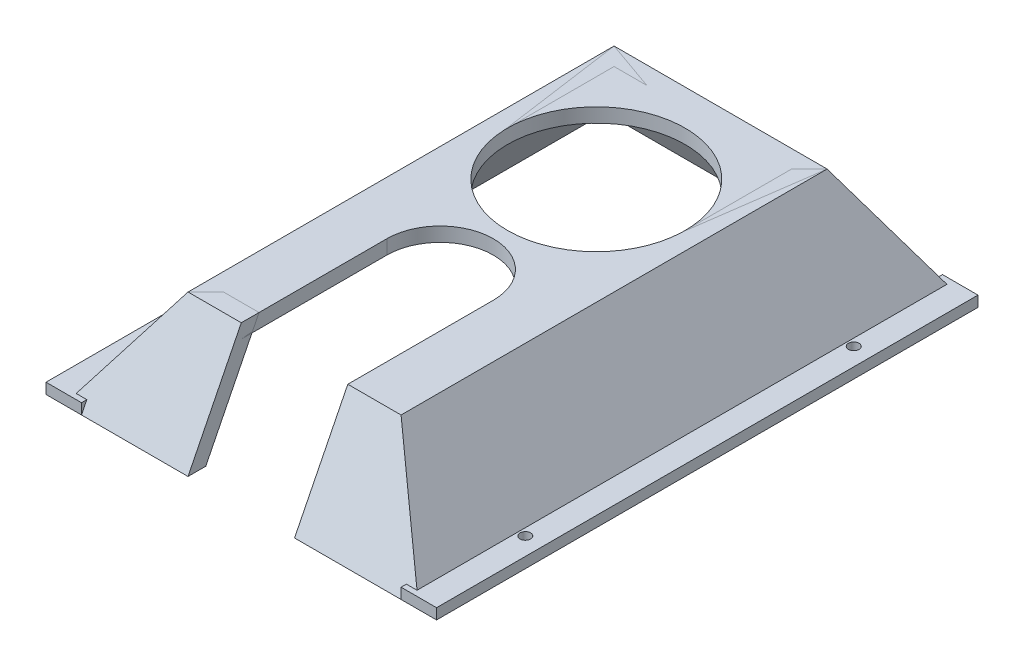
SolidWorks part; units mm, degrees
ref_plane "Front Plane" through (0, 0, 0) normal (0, 0, 1) x (1, 0, 0)
ref_plane "Top Plane" through (0, 0, 0) normal (0, 1, 0) x (1, 0, 0)
ref_plane "Right Plane" through (0, 0, 0) normal (1, 0, 0) x (0, 0, -1)
sketch "Sketch1" plane through (0, 0, 0) normal (0, 1, 0) x (1, 0, 0)
  line L20 (-50, 152.5) -> (50, 152.5)
  line L21 (-50, 152.5) -> (-50, 0)
  line L22 (-50, 0) -> (50, 0)
  line L23 (50, 152.5) -> (50, 0)
  point P4 (0, 0)
  dimension "D1" = 152.5
  dimension "D2" = 100
ref_plane "Plane1" through (0, 30, 0) normal (0, 1, 0) x (1, 0, 0)
sketch "Sketch3" plane through (0, 30, 0) normal (0, 1, 0) x (1, 0, 0)
  line L1 (-30, 135) -> (30, 135)
  line L2 (-30, 135) -> (-30, 15)
  line L3 (-30, 15) -> (30, 15)
  line L4 (30, 135) -> (30, 15)
  point P4 (0, 15)
  dimension "D1" = 120
  dimension "D2" = 60
  dimension "D3" = 15
loft "Loft8" add profiles "Sketch1", "Sketch3" connector at (50, 0, -152.5) connector at (30, 30, -135)
sketch "Sketch4" plane through (0, 30, 0) normal (0, 1, 0) x (1, 0, 0)
  line L0 (30, 135) -> (-30, 135) construction
  line L1 (-25, 130) -> (25, 130)
  line L2 (-25, 130) -> (-25, 20)
  line L3 (-25, 20) -> (25, 20)
  line L4 (25, 130) -> (25, 20)
  line L5 (-30, 15) -> (30, 15) construction
  line L6 (-30, 135) -> (-30, 15) construction
  point P8 (0, 20)
  dimension "D1" = 5
  dimension "D2" = 5
  dimension "D3" = 5
sketch "Sketch5" plane through (0, 0, 0) normal (0, 1, 0) x (1, 0, 0)
  line L0 (-50, 0) -> (50, 0) construction
  line L1 (-45, 147.5) -> (45, 147.5)
  line L2 (-45, 147.5) -> (-45, 5)
  line L3 (-45, 5) -> (45, 5)
  line L4 (45, 147.5) -> (45, 5)
  line L5 (-50, 152.5) -> (50, 152.5) construction
  line L6 (50, 152.5) -> (50, 0) construction
  point P10 (0, 5)
  dimension "D1" = 5
  dimension "D2" = 5
  dimension "D3" = 5
loft "Cut-Loft1" cut profiles "Sketch4", "Sketch5" connector at (25, 30, -130) connector at (45, 0, -147.5)
sketch "Sketch6" plane through (0, 0, 0) normal (0, 1, 0) x (1, 0, 0)
  line L14 (-45, 152.5) -> (-55, 152.5)
  line L15 (-50, 152.5) -> (50, 152.5) construction
  line L16 (-55, 152.5) -> (-55, 0)
  line L17 (-55, 0) -> (-45, 0)
  line L18 (-50, 0) -> (50, 0) construction
  line L19 (-45, 0) -> (-45, 152.5)
  line L20 (0, 150) -> (0, 0) construction
  line L21 (55, 0) -> (45, 0)
  line L22 (55, 152.5) -> (55, 0)
  line L23 (45, 152.5) -> (55, 152.5)
  line L24 (45, 0) -> (45, 152.5)
  line L25 (-50, 0) -> (-50, 30)
  line L26 (-50, 152.5) -> (-50, 122.5)
  point P10 (-50, 30)
  point P11 (-50, 122.5)
  point P26 (50, 30)
  point P27 (50, 122.5)
  dimension "D1" = 10
  dimension "D2" = 152.5
  dimension "D3" = 45
  dimension "D5" = 30
extrude "Boss-Extrude2" add sketch "Sketch6" along normal blind 3 contours L17 L19 L14 L16 | L24 L21 L22 L23 region at (-50, 0, -76.25) region at (50, 0, -76.25)
hole_wizard "Ø3.0mm Dowel Hole1" positions "Sketch9" profile "Sketch10" hole size "Ø3.0" standard "ANSI Metric" end condition through all
sketch "Sketch9" plane through (0, 3, 0) normal (0, 1, 0) x (1, 0, 0)
  point P0 (50, 30)
  point P3 (-50, 30)
  point P6 (-50, 122.5)
  point P9 (50, 122.5)
sketch "Sketch10" plane through (50, 3, -30) normal (1, 0, 0) x (0, 0, 1)
  line L0 (0, 0) -> (0, 3.0001)
  line L1 (0, 3.0001) -> (1.5, 3.0001)
  line L2 (1.5, 3.0001) -> (1.5, 0)
  line L5 (1.5, 0) -> (0, 0)
  line L11 (0, -6.35) -> (0, 107.95) construction
  dimension "Thru Hole Dia." = 3
  dimension "Thru Hole Depth" = 3.0001
sketch "Sketch12" plane through (0, 30, 0) normal (0, 1, 0) x (1, 0, 0)
  line L0 (-15, 56) -> (-15, 15)
  line L2 (0, 1) -> (0, 63.6102) construction
  line L7 (15, 56) -> (15, 15)
  line L12 (-30, 135) -> (30, 135)
  line L13 (-30, 135) -> (-30, 15)
  line L14 (-30, 15) -> (30, 15)
  line L15 (30, 135) -> (30, 15)
  arc A0 (-15, 56) -> (15, 56) centre (0, 56) cw
  circle A2 centre (0, 100) radius 25
  point P16 (0, 71)
  dimension "D3" = 15
  dimension "D5" = 29
  dimension "D6" = 50
  dimension "D1" = 15
  dimension "D2" = 41
extrude "Boss-Extrude3" add sketch "Sketch12" against normal blind 4 separate body contours A0 L2 A2 L13 L14 | L2 A0 L14 L15 A2 region at (-16.3416, 30, -35.5)
sketch "Sketch13" plane through (0, 30, 0) normal (0, 1, 0) x (1, 0, 0)
  line L0 (-25, 20) -> (25, 20) construction
  line L1 (-15, 20) -> (15, 20)
  line L2 (-15, 20) -> (-15, 0)
  line L3 (-15, 0) -> (15, 0)
  line L4 (15, 20) -> (15, 0)
  line L5 (-15, 56) -> (-15, 15) construction
  line L6 (15, 56) -> (15, 15) construction
  dimension "D1" = 20
extrude "Cut-Extrude1" cut sketch "Sketch13" against normal blind 30
